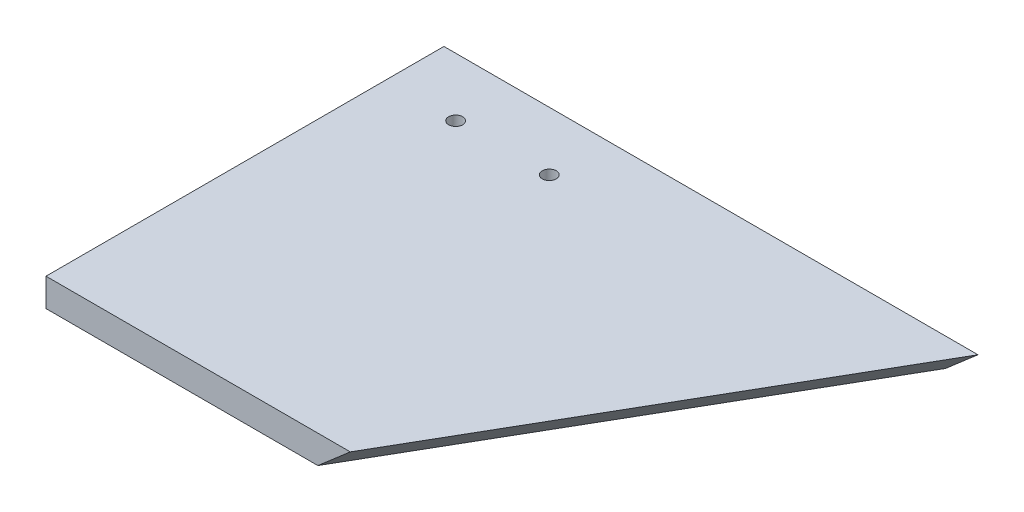
SolidWorks part; units mm, degrees
ref_plane "Front" through (0, 0, 0) normal (0, 0, 1) x (1, 0, 0)
ref_plane "Top" through (0, 0, 0) normal (0, 1, 0) x (1, 0, 0)
ref_plane "Right" through (0, 0, 0) normal (1, 0, 0) x (0, 0, -1)
sketch "Sketch1" plane through (0, 0, 0) normal (0, 1, 0) x (1, 0, 0)
  line L0 (0, 0) -> (49.0748, 85)
  line L1 (0, 0) -> (-65, 0)
  line L3 (0, 85) -> (-65, 85)
  line L4 (-65, 0) -> (-65, 85)
  line L5 (49.0748, 85) -> (0, 85)
  dimension "D1" = 65
  dimension "D2" = 85
  dimension "D3" = 120
extrude "Boss-Extrude1" add sketch "Sketch1" along normal blind 6
sketch "Sketch2" plane through (0, 6, 0) normal (0, 1, 0) x (1, 0, 0)
  line L0 (-65, 85) -> (-65, 0) construction
  line L1 (49.0748, 85) -> (-65, 85) construction
  circle A0 centre (-50, 72.5) radius 1.5
  circle A1 centre (-30, 72.5) radius 1.5
  dimension "D1" = 3
  dimension "D2" = 20
  dimension "D3" = 15
  dimension "D4" = 12.5
extrude "Cut-Extrude1" cut sketch "Sketch2" against normal through all
chamfer "Chamfer1" distance 6 angle 45 1 edges at (24.5374, 0, -42.5)
